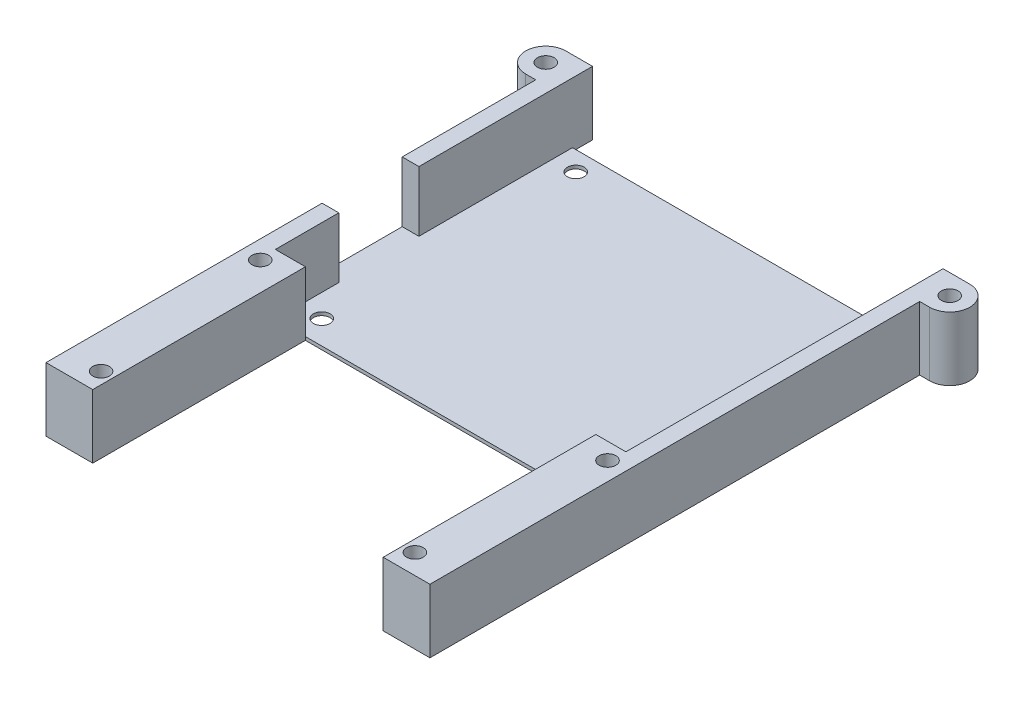
SolidWorks part; units mm, degrees
ref_plane "Front Plane" through (0, 0, 0) normal (0, 0, 1) x (1, 0, 0)
ref_plane "Top Plane" through (0, 0, 0) normal (0, 1, 0) x (1, 0, 0)
ref_plane "Right Plane" through (0, 0, 0) normal (1, 0, 0) x (0, 0, -1)
sketch "Sketch1" plane through (0, 0, 0) normal (0, 1, 0) x (1, 0, 0)
  line L0 (0, 0) -> (0, 76.35) construction
  line L1 (-28.75, 76.35) -> (28.75, 76.35)
  line L2 (28.75, 76.35) -> (28.75, 0)
  line L3 (28.75, 0) -> (21.75, 0)
  line L4 (21.75, 0) -> (21.75, 31.85)
  line L5 (21.75, 31.85) -> (-21.75, 31.85)
  line L6 (-21.75, 31.85) -> (-21.75, 0)
  line L7 (-21.75, 0) -> (-28.75, 0)
  line L8 (-28.75, 0) -> (-28.75, 76.35)
  line L9 (-26.25, 76.35) -> (-26.25, 31.85)
  line L14 (-26.25, 31.85) -> (-21.75, 31.85)
  line L15 (26.25, 76.35) -> (26.25, 31.85)
  line L16 (26.25, 31.85) -> (21.75, 31.85)
  line L17 (28.75, 79.35) -> (30.25, 79.35)
  line L18 (-28.75, 41.35) -> (-26.25, 41.35)
  line L19 (-28.75, 41.35) -> (-28.75, 53.35)
  line L20 (-28.75, 53.35) -> (-26.25, 53.35)
  line L21 (-26.25, 41.35) -> (-26.25, 53.35)
  line L22 (30.25, 73.35) -> (28.75, 73.35)
  line L23 (-30.25, 73.35) -> (-28.75, 73.35)
  line L24 (-28.75, 79.35) -> (-30.25, 79.35)
  line L25 (26.25, 76.35) -> (26.25, 79.35)
  line L26 (26.25, 79.35) -> (28.75, 79.35)
  line L28 (-28.75, 76.35) -> (-28.75, 79.35)
  line L29 (-28.75, 79.35) -> (-26.25, 79.35)
  line L30 (-26.25, 79.35) -> (-26.25, 76.35)
  arc A0 (30.25, 73.35) -> (30.25, 79.35) centre (30.25, 76.35) ccw
  arc A1 (-30.25, 73.35) -> (-30.25, 79.35) centre (-30.25, 76.35) cw
  point P10 (0, 76.35)
  point P16 (-27.5, 41.35)
  point P17 (-22.85, 73.45)
  point P18 (22.85, 73.45)
  point P23 (22.85, 35.4)
  point P24 (-22.85, 35.4)
  point P25 (23.5, 3)
  point P26 (26, 29.35)
  point P27 (-26, 29.35)
  point P28 (-23.5, 3)
  point P40 (30.25, 76.35)
  point P41 (-30.25, 76.35)
  dimension "D16" = 3
  dimension "D1" = 2.5
  dimension "D2" = 7
  dimension "D3" = 43.5
  dimension "D4" = 31.85
  dimension "D5" = 44.5
  dimension "D6" = 23
  dimension "D7" = 12
  dimension "D8" = 22.85
  dimension "D9" = 38.05
  dimension "D10" = 2.9
  dimension "D11" = 47
  dimension "D12" = 52
  dimension "D13" = 47
  dimension "D14" = 3
  dimension "D15" = 1.5
extrude "Boss-Extrude1" add sketch "Sketch1" along normal blind 0.5 contours L5 L0 L1 L9 L14 | L0 L5 L16 L15 L1 | L20 L8 L18 L9 region at (-13.125, 0, -54.1) region at (13.125, 0, -54.1) region at (-27.5, 0, -47.35)
extrude "Boss-Extrude2" add sketch "Sketch1<3>" along normal blind 9.55 contours L18 L8 L7 L6 L14 L9 | L8 L20 L9 L1 | L15 L16 L4 L3 L2 L1 | A1 L23 L8 L24 | L22 A0 L17 L2 | L26 L25 L1 | L30 L29 L28 L1 region at (-27.5, 0, -77.85) region at (-27.5, 0, -64.85) region at (-30.7362, 0, -76.35) region at (29.944, 0, -76.7172) region at (25.999, 0, -28.6329) region at (-25.4666, 0, -17.9154)
sketch "Sketch1<3>" plane through (0, 0, 0) normal (0, 1, 0) x (1, 0, 0) same geometry as "Sketch1"
hole_wizard "Ø2.5 (2.5) Diameter Hole1" positions "Sketch4" profile "Sketch5" hole size "Ø2.5" standard "ANSI Metric"
sketch "Sketch4" plane through (0, 0, 0) normal (0, -1, 0) x (-1, 0, 0)
  point P0 (-22.85, 73.45)
  point P3 (22.85, 73.45)
  point P6 (26, 29.35)
  point P9 (22.85, 35.4)
  point P12 (-22.85, 35.4)
  point P15 (-26, 29.35)
  point P18 (-23.5, 3)
  point P21 (23.5, 3)
  point P24 (-30.25, 76.35)
  point P27 (30.25, 76.35)
sketch "Sketch5" plane through (22.85, 0, -73.45) normal (1, 0, 0) x (0, 0, -1)
  line L0 (0, 0) -> (0, 12.7511)
  line L1 (0, 12.7511) -> (1.25, 12)
  line L2 (1.25, 12) -> (1.25, 0)
  line L5 (1.25, 0) -> (0, 0)
  line L10 (0, 12.7511) -> (-1.25, 12) construction
  line L11 (0, -6.35) -> (0, 107.95) construction
  dimension "Hole Dia." = 2.5
  dimension "Hole Depth" = 12
  dimension "Drill Angle" = 118
